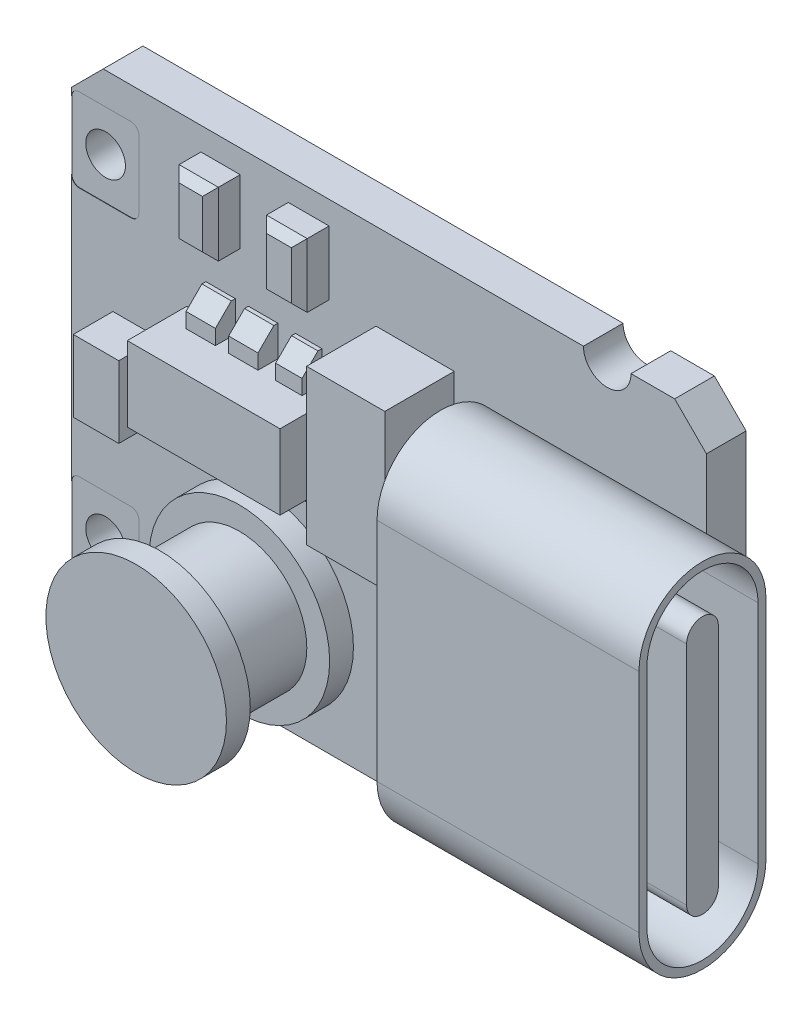
SolidWorks part; units mm, degrees
ref_plane "Plan de face" through (0, 0, 0) normal (0, 0, 1) x (1, 0, 0)
ref_plane "Plan de dessus" through (0, 0, 0) normal (0, 1, 0) x (1, 0, 0)
ref_plane "Plan de droite" through (0, 0, 0) normal (1, 0, 0) x (0, 0, -1)
sketch "Esquisse1" plane through (0, 0, 0) normal (0, 0, 1) x (1, 0, 0)
  line L0 (0, 11.3) -> (0.8, 12.1)
  line L1 (0.8, 0) -> (12.9, 0)
  line L2 (0, 0.8) -> (0, 11.3)
  line L3 (0.8, 12.1) -> (12.9, 12.1)
  line L4 (16, 0.8) -> (16, 11.3)
  line L5 (15.2, 12.1) -> (16, 11.3)
  line L6 (15.2, 0) -> (16, 0.8)
  line L7 (0, 0.8) -> (0.8, 0)
  line L8 (16, 6.05) -> (-1.3, 6.05) construction
  line L9 (14.1, 12.1) -> (15.2, 12.1)
  line L10 (14.1, 0) -> (15.2, 0)
  arc A0 (12.9, 12.1) -> (14.1, 12.1) centre (13.5, 12.1) ccw
  arc A1 (12.9, 0) -> (14.1, 0) centre (13.5, 0) cw
  point P0 (0, 0)
  point P1 (16, 12.1)
  point P2 (0, 12.1)
  point P3 (16, 0)
  dimension "D3" = 2.5
  dimension "D1" = 12.1
  dimension "D2" = 16
extrude "Boss.-Extru.1" add sketch "Esquisse1" along normal blind 1
sketch "Esquisse2" plane through (0, 0, 1) normal (0, 0, 1) x (1, 0, 0)
  line L0 (12.9, 12.1) -> (0.8, 12.1) construction
  line L1 (0, 11.3) -> (0, 0.8) construction
  line L2 (0, 6.05) -> (16, 6.05) construction
  line L3 (16, 0.8) -> (16, 11.3) construction
  circle A0 centre (0.85, 10.25) radius 0.5
  circle A1 centre (0.85, 1.85) radius 0.5
  dimension "D1" = 1
  dimension "D2" = 1.85
  dimension "D3" = 0.85
extrude "Enlèv. mat.-Extru.1" cut sketch "Esquisse2" against normal blind 10
sketch "Esquisse3" plane through (0, 0, 1) normal (0, 0, 1) x (1, 0, 0)
  line L1 (1.5, 9.2) -> (0.2, 9.2)
  line L2 (1.7, 9.4) -> (1.7, 11.1)
  line L3 (1.5, 11.3) -> (0.2, 11.3)
  line L4 (0, 9.4) -> (0, 11.1)
  line L5 (1.7, 9.2) -> (0, 11.3) construction
  line L6 (1.7, 11.3) -> (0, 9.2) construction
  line L7 (1.5, 2.9) -> (0.2, 2.9)
  line L8 (1.7, 2.7) -> (1.7, 1)
  line L9 (1.5, 0.8) -> (0.2, 0.8)
  line L10 (0, 2.7) -> (0, 1)
  line L11 (1.7, 2.9) -> (0, 0.8) construction
  line L12 (1.7, 0.8) -> (0, 2.9) construction
  arc A0 (0.2, 2.9) -> (0, 2.7) centre (0.2, 2.7) ccw
  arc A1 (1.7, 1) -> (1.5, 0.8) centre (1.5, 1) cw
  arc A2 (0.2, 0.8) -> (0, 1) centre (0.2, 1) cw
  arc A3 (1.5, 2.9) -> (1.7, 2.7) centre (1.5, 2.7) cw
  arc A4 (0.2, 11.3) -> (0, 11.1) centre (0.2, 11.1) ccw
  arc A5 (0.2, 9.2) -> (0, 9.4) centre (0.2, 9.4) cw
  arc A6 (1.5, 9.2) -> (1.7, 9.4) centre (1.5, 9.4) ccw
  arc A7 (1.7, 11.1) -> (1.5, 11.3) centre (1.5, 11.1) ccw
  point P0 (0.85, 10.25)
  point P7 (0.85, 1.85)
  dimension "D1" = 0.2
extrude "Enlèv. mat.-Extru.2" cut sketch "Esquisse3" against normal blind 0.01
extrude "Enlèv. mat.-Extru.3" cut sketch "Esquisse3<2>" along normal blind 0.01 from surface starting at face at (1.35, 10.25, 0)
sketch "Esquisse3<2>" plane through (0, 0, 1) normal (0, 0, 1) x (1, 0, 0) same geometry as "Esquisse3"
sketch "Esquisse4" plane through (16, 0, 0) normal (1, 0, 0) x (0, 0, -1)
  line L0 (-1, 6.05) -> (-4.2, 6.05) construction
  line L1 (-1, 0.8) -> (-1, 11.3) construction
  line L2 (-2.6, 6.05) -> (-2.6, 8.9) construction
  line L3 (-2.6, 3.2) -> (-2.6, 8.9) construction
  line L4 (-4.2, 3.2) -> (-4.2, 8.9)
  line L5 (-1, 3.2) -> (-1, 8.9)
  arc A0 (-4.2, 3.2) -> (-1, 3.2) centre (-2.6, 3.2) ccw
  arc A1 (-1, 8.9) -> (-4.2, 8.9) centre (-2.6, 8.9) ccw
  point P8 (-2.6, 6.05)
  dimension "D1" = 3.2
  dimension "D2" = 2.85
  dimension "D3" = 3.2
extrude "Boss.-Extru.2" add sketch "Esquisse4" against normal blind 5.1 and the other way blind 1.5
sketch "Esquisse5" plane through (0, 0, 1) normal (0, 0, 1) x (1, 0, 0)
  circle A0 centre (4.8302, 2.6273) radius 2.2753
extrude "Boss.-Extru.3" add sketch "Esquisse5" along normal blind 3.2
sketch "Esquisse6" plane through (0, 0, 4.2) normal (0, 0, 1) x (1, 0, 0)
  circle A0 centre (4.8302, 2.6273) radius 2.2753
  circle A1 centre (4.8302, 2.6273) radius 1.7
extrude "Enlèv. mat.-Extru.4" cut sketch "Esquisse6" against normal blind 2 from offset 0.6 offset against normal yes
sketch "Esquisse7" plane through (0, 0, 1) normal (0, 0, 1) x (1, 0, 0)
  line L0 (4.1272, 7.9741) -> (4.4602, 7.9741)
  line L1 (2.9061, 6.087) -> (3.3871, 6.087)
  line L2 (2.9061, 6.087) -> (2.9061, 7.9741)
  line L3 (2.9061, 7.9741) -> (3.3871, 7.9741)
  line L4 (6.7543, 6.087) -> (6.7543, 7.9741)
  line L5 (2.9061, 6.087) -> (6.7543, 7.9741) construction
  line L6 (2.9061, 7.9741) -> (6.7543, 6.087) construction
  line L7 (3.3871, 5.31) -> (4.1272, 5.31)
  line L8 (3.3871, 5.31) -> (3.3871, 6.087)
  line L9 (3.3871, 8.7512) -> (4.1272, 8.7512)
  line L10 (4.1272, 5.31) -> (4.1272, 6.087)
  line L11 (3.3871, 5.31) -> (4.1272, 8.7512) construction
  line L12 (3.3871, 8.7512) -> (4.1272, 5.31) construction
  line L13 (4.4602, 5.31) -> (5.2003, 5.31)
  line L14 (4.4602, 5.31) -> (4.4602, 6.087)
  line L15 (4.4602, 8.7512) -> (5.2003, 8.7512)
  line L16 (5.2003, 5.31) -> (5.2003, 6.087)
  line L17 (4.4602, 5.31) -> (5.2003, 8.7512) construction
  line L18 (4.4602, 8.7512) -> (5.2003, 5.31) construction
  line L19 (5.6443, 5.31) -> (6.3103, 5.31)
  line L20 (5.6443, 5.31) -> (5.6443, 6.087)
  line L21 (5.6443, 8.7512) -> (6.3103, 8.7512)
  line L22 (6.3103, 5.31) -> (6.3103, 6.087)
  line L23 (5.6443, 5.31) -> (6.3103, 8.7512) construction
  line L24 (5.6443, 8.7512) -> (6.3103, 5.31) construction
  line L25 (4.1272, 7.9741) -> (4.1272, 8.7512)
  line L26 (3.3871, 7.9741) -> (3.3871, 8.7512)
  line L27 (4.1272, 6.087) -> (4.4602, 6.087)
  line L28 (5.2003, 7.9741) -> (5.6443, 7.9741)
  line L29 (4.4602, 7.9741) -> (4.4602, 8.7512)
  line L30 (5.2003, 7.9741) -> (5.2003, 8.7512)
  line L31 (5.2003, 6.087) -> (5.6443, 6.087)
  line L32 (5.6443, 7.9741) -> (5.6443, 8.7512)
  line L33 (6.3103, 7.9741) -> (6.3103, 8.7512)
  line L34 (6.3103, 7.9741) -> (6.7543, 7.9741)
  line L35 (6.3103, 6.087) -> (6.7543, 6.087)
  line L37 (7.6743, 6.0249) -> (9.6452, 6.0249)
  line L38 (7.6743, 6.0249) -> (7.6743, 9.9234)
  line L39 (7.6743, 9.9234) -> (9.6452, 9.9234)
  line L40 (9.6452, 6.0249) -> (9.6452, 9.9234)
  line L41 (7.6743, 6.0249) -> (9.6452, 9.9234) construction
  line L42 (7.6743, 9.9234) -> (9.6452, 6.0249) construction
  line L43 (3.2622, 9.9054) -> (4.2521, 9.9054)
  line L44 (3.2622, 9.9054) -> (3.2622, 11.518)
  line L45 (3.2622, 11.518) -> (4.2521, 11.518)
  line L46 (4.2521, 9.9054) -> (4.2521, 11.518)
  line L47 (3.2622, 9.9054) -> (4.2521, 11.518) construction
  line L48 (3.2622, 11.518) -> (4.2521, 9.9054) construction
  line L49 (5.4636, 9.9054) -> (6.491, 9.9054)
  line L50 (5.4636, 9.9054) -> (5.4636, 11.518)
  line L51 (5.4636, 11.518) -> (6.491, 11.518)
  line L52 (6.491, 9.9054) -> (6.491, 11.518)
  line L53 (5.4636, 9.9054) -> (6.491, 11.518) construction
  line L54 (5.4636, 11.518) -> (6.491, 9.9054) construction
  line L55 (2.1916, 6.9282) -> (1.0449, 6.9282)
  line L56 (2.1916, 6.9282) -> (2.1916, 5.1215)
  line L57 (2.1916, 5.1215) -> (1.0449, 5.1215)
  line L58 (1.0449, 6.9282) -> (1.0449, 5.1215)
  line L59 (2.1916, 6.9282) -> (1.0449, 5.1215) construction
  line L60 (2.1916, 5.1215) -> (1.0449, 6.9282) construction
  point P0 (4.8302, 7.0306)
  point P5 (3.7572, 7.0306)
  point P10 (4.8302, 7.0306)
  point P15 (5.9773, 7.0306)
  point P26 (8.6597, 7.9741)
  point P37 (3.7572, 10.7117)
  point P42 (5.9773, 10.7117)
  point P47 (1.6183, 6.0249)
extrude "Boss.-Extru.4" add sketch "Esquisse7" along normal blind 1.5
sketch "Esquisse8" plane through (0, 0, 1) normal (0, 0, 1) x (1, 0, 0)
  line L1 (7.9199, 5.5505) -> (9.178, 5.5505)
  line L2 (7.9199, 5.5505) -> (7.9199, 4.8844)
  line L3 (7.9199, 4.8844) -> (9.178, 4.8844)
  line L4 (9.178, 5.5505) -> (9.178, 4.8844)
  line L5 (7.9199, 5.5505) -> (9.178, 4.8844) construction
  line L6 (7.9199, 4.8844) -> (9.178, 5.5505) construction
  line L7 (10.4267, 4.4746) -> (9.733, 4.4746)
  line L8 (10.4267, 4.4746) -> (10.4267, 3.2193)
  line L9 (10.4267, 3.2193) -> (9.733, 3.2193)
  line L10 (9.733, 4.4746) -> (9.733, 3.2193)
  line L11 (10.4267, 4.4746) -> (9.733, 3.2193) construction
  line L12 (10.4267, 3.2193) -> (9.733, 4.4746) construction
  point P0 (8.549, 5.2175)
  point P5 (10.0798, 3.847)
extrude "Boss.-Extru.5" add sketch "Esquisse8" along normal blind 0.5
sketch "Esquisse9" plane through (0, 0, 2.5) normal (0, 0, 1) x (1, 0, 0)
  line L0 (2.9061, 7.9741) -> (2.9061, 8.7512)
  line L1 (2.9061, 6.087) -> (6.7543, 6.087)
  line L3 (2.9061, 7.9741) -> (6.7543, 7.9741)
  line L5 (2.9061, 5.31) -> (6.7543, 5.31)
  line L6 (2.9061, 5.31) -> (2.9061, 6.087)
  line L7 (2.9061, 8.7512) -> (6.7543, 8.7512)
  line L8 (6.7543, 5.31) -> (6.7543, 6.087)
  line L9 (6.7543, 7.9741) -> (6.7543, 8.7512)
extrude "Enlèv. mat.-Extru.5" cut sketch "Esquisse9" against normal blind 1
chamfer "Chanfrein1" distance 0.4 angle 45 6 edges at (3.7572, 5.31, 1.5) (4.8302, 5.31, 1.5) (5.9773, 5.31, 1.5) (5.9773, 8.7512, 1.5) (4.8302, 8.7512, 1.5) (3.7572, 8.7512, 1.5)
sketch "Esquisse10" plane through (0, 0, 2.5) normal (0, 0, 1) x (1, 0, 0)
  line L1 (6.491, 11.518) -> (3.2622, 11.518)
  line L2 (6.491, 11.518) -> (6.491, 9.9054)
  line L3 (6.491, 9.9054) -> (3.2622, 9.9054)
  line L4 (3.2622, 11.518) -> (3.2622, 9.9054)
extrude "Enlèv. mat.-Extru.6" cut sketch "Esquisse10" against normal blind 0.75
sketch "Esquisse11" plane through (0, 0, 2.5) normal (0, 0, 1) x (1, 0, 0)
  line L1 (1.0449, 5.1215) -> (2.2586, 5.1215)
  line L2 (1.0449, 5.1215) -> (1.0449, 7.0491)
  line L3 (1.0449, 7.0491) -> (2.2586, 7.0491)
  line L4 (2.2586, 5.1215) -> (2.2586, 7.0491)
extrude "Enlèv. mat.-Extru.7" cut sketch "Esquisse11" against normal blind 0.5
sketch "Esquisse12" plane through (0, 0, 2.5) normal (0, 0, 1) x (1, 0, 0)
  line L1 (9.6452, 9.9234) -> (7.6743, 9.9234)
  line L2 (9.6452, 9.9234) -> (9.6452, 6.0249)
  line L3 (9.6452, 6.0249) -> (7.6743, 6.0249)
  line L4 (7.6743, 9.9234) -> (7.6743, 6.0249)
extrude "Boss.-Extru.6" add sketch "Esquisse12" along normal blind 0.25
chamfer "Chanfrein2" distance 0.2 angle 45 8 edges at (4.2521, 10.7117, 1.75) (3.7572, 9.9054, 1.75) (3.2622, 10.7117, 1.75) (3.7572, 11.518, 1.75) (5.4636, 10.7117, 1.75) (5.9773, 11.518, 1.75) (6.491, 10.7117, 1.75) (5.9773, 9.9054, 1.75)
sketch "Esquisse13" plane through (17.5, 0, 0) normal (1, 0, 0) x (0, 0, -1)
  line L6 (-2.2, 3.2) -> (-2.2, 8.9)
  line L7 (-3, 8.9) -> (-3, 3.2)
  line L8 (-2.2, 3.2) -> (-2.2, 8.9)
  line L9 (-3, 8.9) -> (-3, 3.2)
  line L10 (-1.2, 3.2) -> (-1.2, 8.9)
  line L11 (-4, 8.9) -> (-4, 3.2)
  line L12 (-1.2, 3.2) -> (-1.2, 8.9)
  line L13 (-4, 8.9) -> (-4, 3.2)
  arc A6 (-3, 3.2) -> (-2.2, 3.2) centre (-2.6, 3.2) ccw
  arc A7 (-2.2, 8.9) -> (-3, 8.9) centre (-2.6, 8.9) ccw
  arc A8 (-3, 3.2) -> (-2.2, 3.2) centre (-2.6, 3.2) ccw
  arc A9 (-2.2, 8.9) -> (-3, 8.9) centre (-2.6, 8.9) ccw
  arc A10 (-4, 3.2) -> (-1.2, 3.2) centre (-2.6, 3.2) ccw
  arc A11 (-1.2, 8.9) -> (-4, 8.9) centre (-2.6, 8.9) ccw
  arc A12 (-4, 3.2) -> (-1.2, 3.2) centre (-2.6, 3.2) ccw
  arc A13 (-1.2, 8.9) -> (-4, 8.9) centre (-2.6, 8.9) ccw
  dimension "D1" = 1.2
  dimension "D2" = 0.2
extrude "Enlèv. mat.-Extru.8" cut sketch "Esquisse13" against normal blind 6.25
